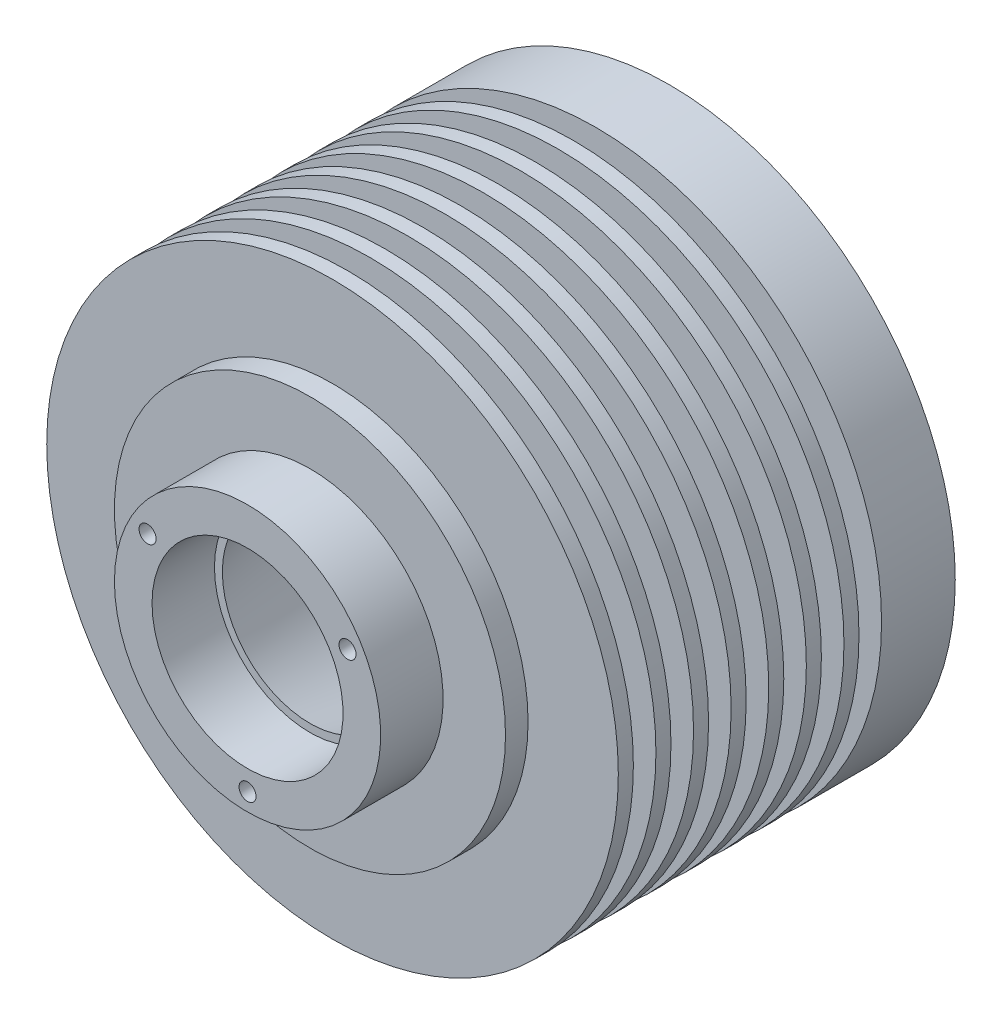
SolidWorks part; units mm, degrees
ref_plane "Plan de face" through (0, 0, 0) normal (0, 0, 1) x (1, 0, 0)
ref_plane "Plan de dessus" through (0, 0, 0) normal (0, 1, 0) x (1, 0, 0)
ref_plane "Plan de droite" through (0, 0, 0) normal (1, 0, 0) x (0, 0, -1)
sketch "Esquisse1" plane through (0, 0, 0) normal (0, 0, 1) x (1, 0, 0)
  circle A0 centre (0, 0) radius 12.7
  circle A1 centre (0, 0) radius 17.7
extrude "Boss.-Extru.1" add sketch "Esquisse1" along normal blind 8.3
sketch "Esquisse2" plane through (0, 0, 0) normal (0, 0, -1) x (-1, 0, 0)
  circle A0 centre (0, 0) radius 11.2
  circle A1 centre (0, 0) radius 38
extrude "Boss.-Extru.2" add sketch "Esquisse2" along normal blind 47.8
chamfer "Chanfrein3" distance 49.8 angle 12.675 1 edges at (-11.2, 0, -47.8)
sketch "Esquisse3" [suppressed] plane through (0, 0, 7.7) normal (0, 0, 1) x (1, 0, 0)
  line L0 (-12.7, 0) -> (-17.7, 0)
  line L1 (12.7, 0) -> (17.7, 0)
  circle A0 centre (0, 0) radius 12.7 construction
  circle A1 centre (0, 0) radius 17.7 construction
  circle A2 centre (0, 0) radius 12.7 construction
other "PerçageAvancé1" [suppressed] parameters "D0"=0
sketch "Esquisse4" plane through (0, 0, 7.7) normal (0, 0, 1) x (1, 0, 0)
  line L0 (-12.7, 0) -> (-17.7, 0) construction
  line L1 (12.7, 0) -> (17.7, 0) construction
  point P0 (-15.2, 0)
  point P4 (15.2, 0)
sketch "Esquisse5" plane through (-15.2, 0, 7.7) normal (0, 1, 0) x (1, 0, 0)
  line L0 (0, 0) -> (0, 1.1176)
  line L1 (0, -0.5588) -> (0, 1.6764) construction
  line L2 (1.7856, 0) -> (1.7856, 1.1176)
  line L3 (0, 0) -> (1.7856, 0)
  line L4 (1.7856, 1.1176) -> (0, 1.1176)
  dimension "D1" = 1.1176
  dimension "D2" = 3.5712
sketch "Sketch1" plane through (0, 0, 8.3) normal (0, 0, 1) x (1, 0, 0)
  line L0 (-12.7, 0) -> (-17.7, 0)
  line L1 (-17.7, 0) -> (12.7, 0)
  line L2 (12.7, 0) -> (17.7, 0)
  circle A0 centre (0, 0) radius 12.7 construction
  circle A1 centre (0, 0) radius 12.7 construction
  circle A2 centre (0, 0) radius 17.7 construction
sketch "Sketch7" plane through (0, 0, 0) normal (0, 0, 1) x (1, 0, 0)
  circle A0 centre (0, 0) radius 26
  circle A1 centre (0, 0) radius 38
extrude "Cut-Extrude2" cut sketch "Sketch7" against normal blind 3
sketch "Sketch12" plane through (0, 0, -47.8) normal (0, 0, -1) x (-1, 0, 0)
  line L0 (38, 0) -> (34, 0)
  circle A0 centre (0, 0) radius 38 construction
sketch "Sketch16" plane through (0, 0, -47.8) normal (0, 0, -1) x (-1, 0, 0)
  line L0 (0, 38) -> (0, -30)
  circle A0 centre (0, 0) radius 38 construction
hole_wizard "#4-40 Tapped Hole1" positions "Sketch17" profile "Sketch19" tap size "#4-40" standard "ANSI Inch"
sketch "Sketch17" plane through (0, 0, -47.8) normal (0, 0, -1) x (-1, 0, 0)
  point P0 (0, -30)
sketch "Sketch19" plane through (0, -30, -47.8) normal (1, 0, 0) x (0, 1, 0)
  line L0 (0, 0) -> (0, 5.6792)
  line L1 (0, 5.6792) -> (1.1303, 5)
  line L2 (1.1303, 5) -> (1.1303, 0)
  line L5 (1.1303, 0) -> (0, 0)
  line L10 (0, 5.6792) -> (-1.1303, 5) construction
  line L11 (0, -6.35) -> (0, 107.95) construction
  dimension "Tap Drill Dia." = 2.2606
  dimension "Tap Drill Depth" = 5
  dimension "Drill Angle" = 118
pattern_circular "CirPattern1" count 4 over 360 about axis through (0, 0, 0) along (0, 0, 1) of "#4-40 Tapped Hole1"
sketch "Sketch20" plane through (0, 0, 8.3) normal (0, 0, 1) x (1, 0, 0)
  line L0 (0, 17.7) -> (0, -15.35)
  circle A0 centre (0, 0) radius 17.7 construction
hole_wizard "#4-40 Tapped Hole2" positions "Sketch21" profile "Sketch22" tap size "#4-40" standard "ANSI Inch"
sketch "Sketch21" plane through (0, 0, 8.3) normal (0, 0, 1) x (1, 0, 0)
  point P0 (0, -15.35)
sketch "Sketch22" plane through (0, -15.35, 8.3) normal (1, 0, 0) x (0, -1, 0)
  line L0 (0, 0) -> (0, 5.6792)
  line L1 (0, 5.6792) -> (1.1303, 5)
  line L2 (1.1303, 5) -> (1.1303, 0)
  line L5 (1.1303, 0) -> (0, 0)
  line L10 (0, 5.6792) -> (-1.1303, 5) construction
  line L11 (0, -6.35) -> (0, 107.95) construction
  dimension "Tap Drill Dia." = 2.2606
  dimension "Tap Drill Depth" = 5
  dimension "Drill Angle" = 118
pattern_circular "CirPattern2" count 3 over 360 about axis through (0, 0, 0) along (0, 0, 1) of "#4-40 Tapped Hole2"
pattern_linear "LPattern1" count 8 spacing 5 along (0, 0, -1) of "Cut-Extrude2"
